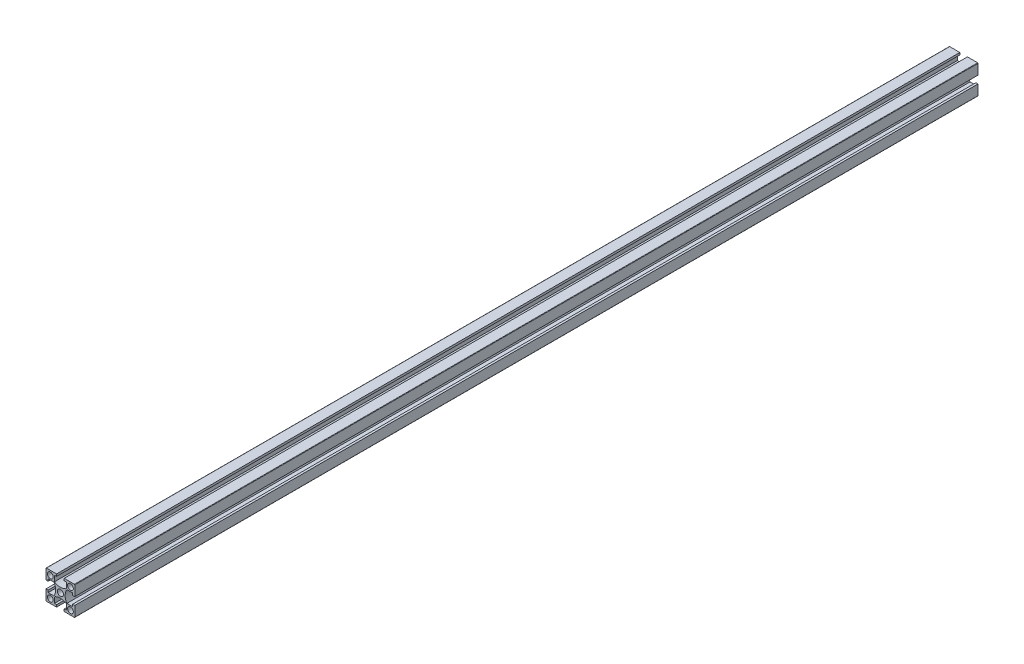
SolidWorks part; units mm, degrees
material "3.0255 (EN-AW 1350A)"
ref_plane "정면" through (0, 0, 0) normal (0, 0, 1) x (1, 0, 0)
ref_plane "윗면" through (0, 0, 0) normal (0, 1, 0) x (1, 0, 0)
ref_plane "우측면" through (0, 0, 0) normal (1, 0, 0) x (0, 0, -1)
sketch "스케치1" plane through (0, 0, 0) normal (0, 0, 1) x (1, 0, 0)
  line L0 (0, 32.0265) -> (0, -31.6588) construction
  line L1 (-10, 10) -> (-10, -10)
  line L2 (-10, 10) -> (10, 10)
  line L3 (-10, 2.65) -> (-8.5, 2.65)
  line L4 (13.6618, 0) -> (-11.6993, 0) construction
  line L5 (-8.5, 2.65) -> (-8.5, 4.15)
  line L6 (-8.5, 4.15) -> (-4.5032, 4.15)
  line L7 (-10, -2.65) -> (-8.5, -2.65)
  line L8 (-8.5, -2.65) -> (-8.5, -4.15)
  line L9 (-8.5, -4.15) -> (-4.5032, -4.15)
  line L10 (-10, -10) -> (10, -10)
  line L11 (10, 10) -> (10, -10)
  circle A0 centre (-7, 7) radius 2
  circle A1 centre (-7, -7) radius 2
  arc A2 (-4.5032, 4.15) -> (-4.5032, -4.15) centre (-11.0587, 0) cw
  circle A3 centre (0, 0) radius 2.15
  circle A4 centre (7, 7) radius 2
  circle A5 centre (7, -7) radius 2
  point P21 (-10, 0)
  point P23 (-3.3, 0)
  point P31 (0, -10)
  point P32 (0, 10)
  dimension "D3" = 4
  dimension "D9" = 6.7
  dimension "D10" = 4.3
  dimension "D11" = 7.7587
  dimension "D1" = 20
  dimension "D2" = 20
  dimension "D4" = 14
  dimension "D5" = 14
  dimension "D6" = 5.3
  dimension "D7" = 8.3
  dimension "D8" = 1.5
extrude "보스-돌출1" add sketch "스케치1" along normal blind 628 contours A0 | A4 | A3 | A5 | A1 | A2 L6 L5 L3 L1 L7 L8 L9 | L2 L11 L10 L1 region at (-6.6069, 0, 0) region at (-7, 7, 0) region at (-7, -7, 0) region at (0, 0, 0) region at (7, 7, 0) region at (7, -7, 0)
extrude "컷-돌출1" cut sketch "스케치1<3>" along normal up to next contours A2 L6 L5 L3 L1 L7 L8 L9 region at (-6.6069, 0, 0)
sketch "스케치1<3>" plane through (0, 0, 0) normal (0, 0, 1) x (1, 0, 0) same geometry as "스케치1"
pattern_circular "원형 패턴1" count 4 over 360 about axis through (0, 0, 628) along (0, 0, -1) of "컷-돌출1" reverse direction yes
fillet "필렛1" radius 0.3 4 edges at (10, -10, 314) (-10, -10, 314) (-10, 10, 314) (10, 10, 314)
sketch "스케치2" plane through (0, 0, 0) normal (1, 0, 0) x (0, 0, -1)
  line L2 (0, -2.65) -> (0, -9.7) construction
  circle A0 centre (-15, 0) radius 2.5
  dimension "D2" = 5
  dimension "D1" = 15
extrude "컷-돌출2" cut sketch "스케치2" against normal through all both and the other way through all
sketch "스케치3" plane through (0, -10, 0) normal (0, -1, 0) x (1, 0, 0)
  line L0 (9.7, 131) -> (-9.7, 131) construction
  line L1 (9.7, 0) -> (9.7, 628) construction
  line L2 (-9.7, 628) -> (-9.7, 0) construction
  line L3 (-9.7, 0) -> (-2.65, 0) construction
  line L4 (9.7, 367) -> (-9.7, 367) construction
  circle A0 centre (0, 141) radius 2.5
  circle A1 centre (0, 357) radius 2.5
  dimension "D1" = 141
  dimension "D4" = 10
  dimension "D2" = 131
  dimension "D3" = 236
extrude "컷-돌출3" cut sketch "스케치3" against normal through all
sketch "스케치4" plane through (0, -10, 0) normal (0, -1, 0) x (1, 0, 0)
  circle A0 centre (0, 249) radius 2.5
  circle A4 centre (0, 141) radius 2.5 construction
  dimension "D1" = 108
extrude "컷-돌출4" cut sketch "스케치4" against normal through all
sketch "스케치5" plane through (0, -10, 0) normal (0, -1, 0) x (1, 0, 0)
  line L0 (-9.7, 485) -> (9.7, 485) construction
  line L1 (-9.7, 628) -> (-9.7, 0) construction
  line L2 (9.7, 0) -> (9.7, 628) construction
  line L3 (-9.7, 433) -> (9.7, 433) construction
  line L4 (-9.7, 295) -> (9.7, 295) construction
  line L5 (-9.7, 248.9) -> (9.7, 248.9) construction
  line L6 (-9.7, 423) -> (9.7, 423) construction
  line L7 (-9.7, 196.9) -> (9.7, 196.9) construction
  line L8 (2.65, 628) -> (9.7, 628) construction
  line L9 (-9.7, 628) -> (-2.65, 628) construction
  line L10 (-9.7, 74.15) -> (9.7, 74.15) construction
  line L11 (-9.7, 2.15) -> (9.7, 2.15) construction
  line L12 (-9.7, 475) -> (9.7, 475) construction
  line L13 (-9.7, 305) -> (9.7, 305) construction
  line L14 (-9.7, 238.9) -> (9.7, 238.9) construction
  line L15 (-9.7, 186.9) -> (9.7, 186.9) construction
  line L16 (-9.7, 64.15) -> (9.7, 64.15) construction
  line L17 (-9.7, 12.15) -> (9.7, 12.15) construction
  line L18 (4.15, 628) -> (-4.15, 628) construction
  circle A0 centre (0, 475) radius 2.15
  circle A2 centre (0, 423) radius 2.15
  circle A3 centre (0, 305) radius 2.12
  circle A4 centre (0, 238.9) radius 2.15
  circle A5 centre (0, 186.9) radius 2.15
  circle A6 centre (0, 64.15) radius 2.15
  circle A7 centre (0, 12.15) radius 2.15
  circle A8 centre (0, 617) radius 2.5
  dimension "D15" = 4.3
  dimension "D16" = 11
  dimension "D1" = 143
  dimension "D2" = 195
  dimension "D3" = 333
  dimension "D4" = 379.1
  dimension "D5" = 431.1
  dimension "D6" = 553.85
  dimension "D7" = 625.85
  dimension "D8" = 10
  dimension "D9" = 10
  dimension "D10" = 10
  dimension "D11" = 10
  dimension "D12" = 10
  dimension "D13" = 10
  dimension "D14" = 10
extrude "컷-돌출5" cut sketch "스케치5" against normal through all
